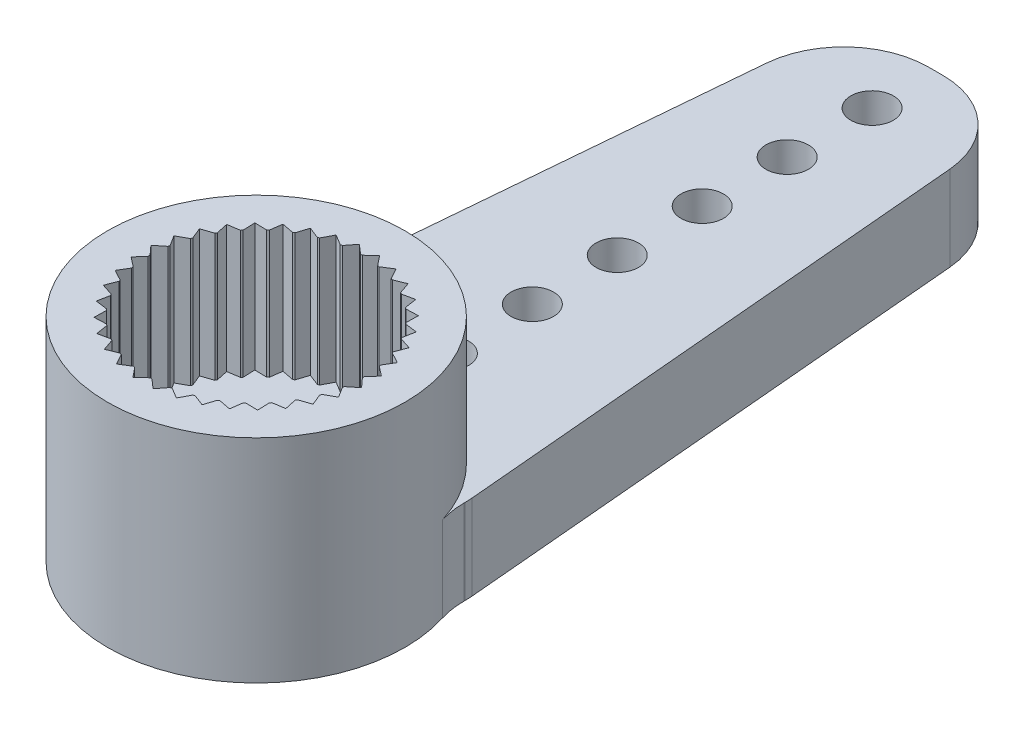
SolidWorks part; units mm, degrees
ref_plane "Front Plane" through (0, 0, 0) normal (0, 0, 1) x (1, 0, 0)
ref_plane "Top Plane" through (0, 0, 0) normal (0, 1, 0) x (1, 0, 0)
ref_plane "Right Plane" through (0, 0, 0) normal (1, 0, 0) x (0, 0, -1)
sketch "Sketch1" plane through (0, 0, 0) normal (0, 1, 0) x (1, 0, 0)
  line L0 (-21.777, 0) -> (33.3507, 0) construction
  line L1 (0, 26.1309) -> (0, -34.4991) construction
  line L2 (-17.4191, 16) -> (29.5794, 16) construction
  line L3 (-18.8664, -16) -> (33.3507, -16) construction
  line L4 (8.5, 26.926) -> (8.5, -27.618) construction
  line L5 (-8.5, 31.6087) -> (-8.5, -32.3009) construction
  line L6 (-24.067, 1.75) -> (35.98, 1.75) construction
  line L7 (-24.067, 0) -> (33.3507, 0) construction
  line L8 (-3.25, 29.5018) -> (-3.25, -36.5148) construction
  line L9 (3.25, 29.5018) -> (3.25, -33.8811) construction
  line L10 (-2, 29.5018) -> (-2, -51.2631) construction
  line L11 (2, 29.5018) -> (2, -51.2631) construction
  line L12 (-3.25, 0) -> (-3.25, 1.75)
  line L13 (-3.25, 1.75) -> (-2, 16)
  line L14 (-2, 16) -> (2, 16)
  line L15 (2, 16) -> (3.25, 1.75)
  line L16 (3.25, 0) -> (3.25, 1.75)
  line L17 (-3.25, 0) -> (3.25, 0)
  dimension "D1" = 16
  dimension "D2" = 16
  dimension "D3" = 8.5
  dimension "D4" = 8.5
  dimension "D5" = 1.75
  dimension "D6" = 0
  dimension "D7" = 3.25
  dimension "D8" = 3.25
  dimension "D9" = 2
  dimension "D10" = 2
extrude "Boss-Extrude1" add sketch "Sketch1" along normal blind 2
fillet "Fillet1" radius 2 2 edges at (-2, 1, -16) (2, 1, -16)
sketch "Sketch2" plane through (0, 2, 0) normal (0, 1, 0) x (1, 0, 0)
  circle A0 centre (0, 0) radius 3.5
extrude "Boss-Extrude2" add sketch "Sketch2" along normal blind 3 and the other way blind 2
sketch "Sketch3" plane through (0, 0, 0) normal (0, -1, 0) x (-1, 0, 0)
  circle A0 centre (0, 0) radius 2.5
extrude "Cut-Extrude1" cut sketch "Sketch3" against normal blind 1
sketch "Sketch4" plane through (0, 1, 0) normal (0, -1, 0) x (-1, 0, 0)
  circle A0 centre (0, 0) radius 1
extrude "Cut-Extrude2" cut sketch "Sketch4" against normal through all
sketch "Sketch5" plane through (0, 5, 0) normal (0, 1, 0) x (1, 0, 0)
  circle A0 centre (0, 0) radius 2.5
extrude "Cut-Extrude3" cut sketch "Sketch5" against normal blind 3
sketch "Sketch6" plane through (0, 5, 0) normal (0, 1, 0) x (1, 0, 0)
  line L0 (-4.6624, 0) -> (4.5112, 0) construction
  line L1 (-5.0093, 0.3942) -> (0, 0) construction
  line L2 (0, 0) -> (6.4397, -0.5068) construction
  line L3 (0, 0) -> (-6.4046, 1.0144) construction
  line L4 (-2.5, 0) -> (-2.6917, 0.2118)
  line L5 (-2.6917, 0.2118) -> (-2.4692, 0.3911)
  line L6 (-2.4692, 0.3911) -> (-2.5, 0)
  circle A0 centre (0, 0) radius 2.7
  circle A1 centre (0, 0) radius 2.5 construction
  dimension "D1" = 4.5
  dimension "D2" = 4.5
extrude "Cut-Extrude4" cut sketch "Sketch6" against normal blind 3 contours L5 L6 L4
sketch "Sketch8" plane through (0, 0, 0) normal (1, 0, 0) x (0, 0, -1)
  line L0 (0, 0) -> (0, 8.8025) construction
pattern_circular "CirPattern1" count 36 over 360 about axis through (0, 0, 0) along (0, 1, 0) of "Cut-Extrude4"
sketch "Sketch9" plane through (0, 0, 0) normal (0, -1, 0) x (-1, 0, 0)
  circle A0 centre (0, 14.5) radius 0.5
  point P2 (0, 0)
  point P3 (0, 0)
extrude "Cut-Extrude5" cut sketch "Sketch9" against normal through all contours A0
sketch "Sketch10" plane through (0, 0, 0) normal (0, -1, 0) x (-1, 0, 0)
  line L0 (0, 13.2867) -> (0, -8.4466) construction
pattern_linear "LPattern1" count 6 spacing 2 along (0, 0, 1) of "Cut-Extrude5"
fillet "Fillet3" radius 2 4 edges at (3.25, 1, -1.75) (3.25, 1, -1.299) (-3.25, 1, -1.75) (-3.25, 1, -1.299)
